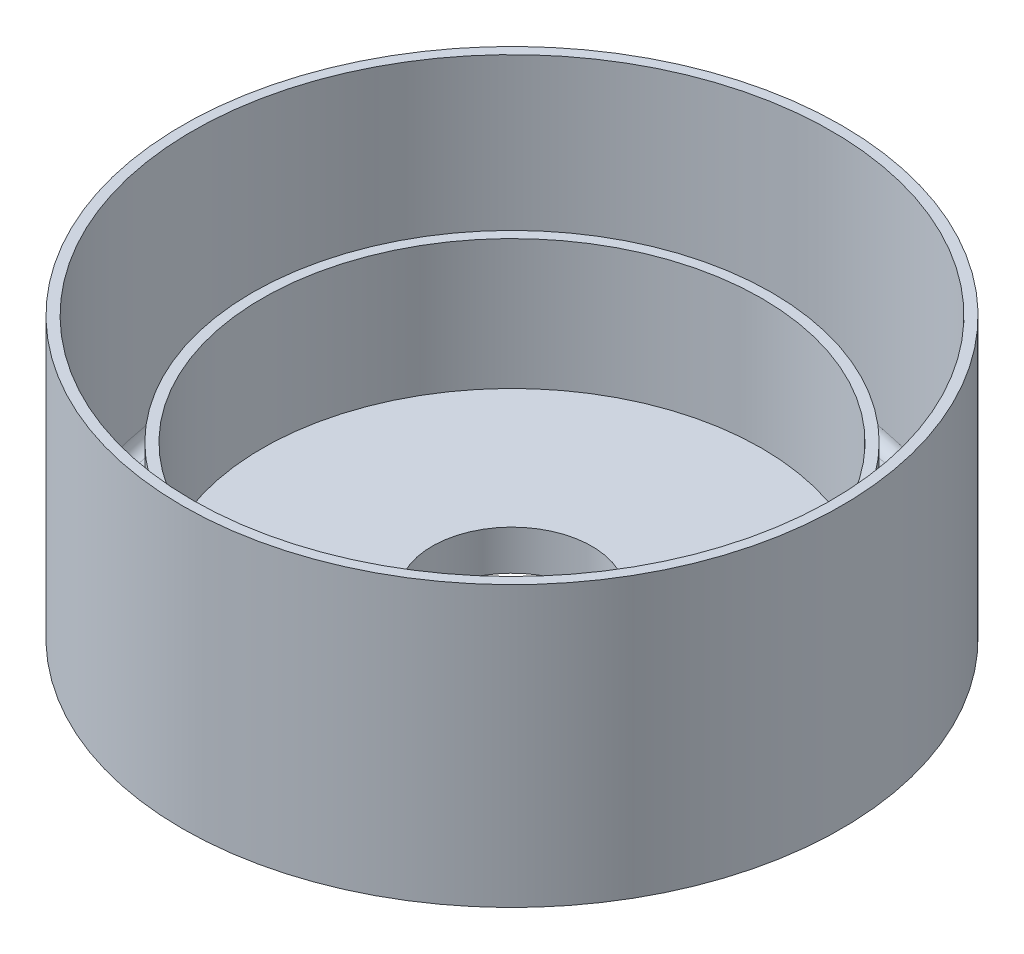
SolidWorks part; units mm, degrees
ref_plane "Front Plane" through (0, 0, 0) normal (0, 0, 1) x (1, 0, 0)
ref_plane "Top Plane" through (0, 0, 0) normal (0, 1, 0) x (1, 0, 0)
ref_plane "Right Plane" through (0, 0, 0) normal (1, 0, 0) x (0, 0, -1)
sketch "Sketch11" plane through (0, 0, 0) normal (0, 1, 0) x (1, 0, 0)
  circle A0 centre (0, 0) radius 80
  circle A1 centre (0, 0) radius 20
  circle A2 centre (0, 0) radius 65
  circle A3 centre (0, 0) radius 62.5
  circle A4 centre (0, 0) radius 82.5
extrude "Boss-Extrude7" add sketch "Sketch11" along normal blind 10 contours A4 | A1
extrude "Boss-Extrude8" add sketch "Sketch11<9>" along normal blind 70 contours A4 | A0
sketch "Sketch11<9>" plane through (0, 0, 0) normal (0, 1, 0) x (1, 0, 0) same geometry as "Sketch11"
extrude "Boss-Extrude9" add sketch "Sketch11<10>" along normal blind 42.5 contours A2 | A3
sketch "Sketch11<10>" plane through (0, 0, 0) normal (0, 1, 0) x (1, 0, 0) same geometry as "Sketch11"
fillet "Fillet2" radius 3 1 edges at (0, 10, 80)
fillet "Fillet3" radius 3 1 edges at (0, 10, 65)
